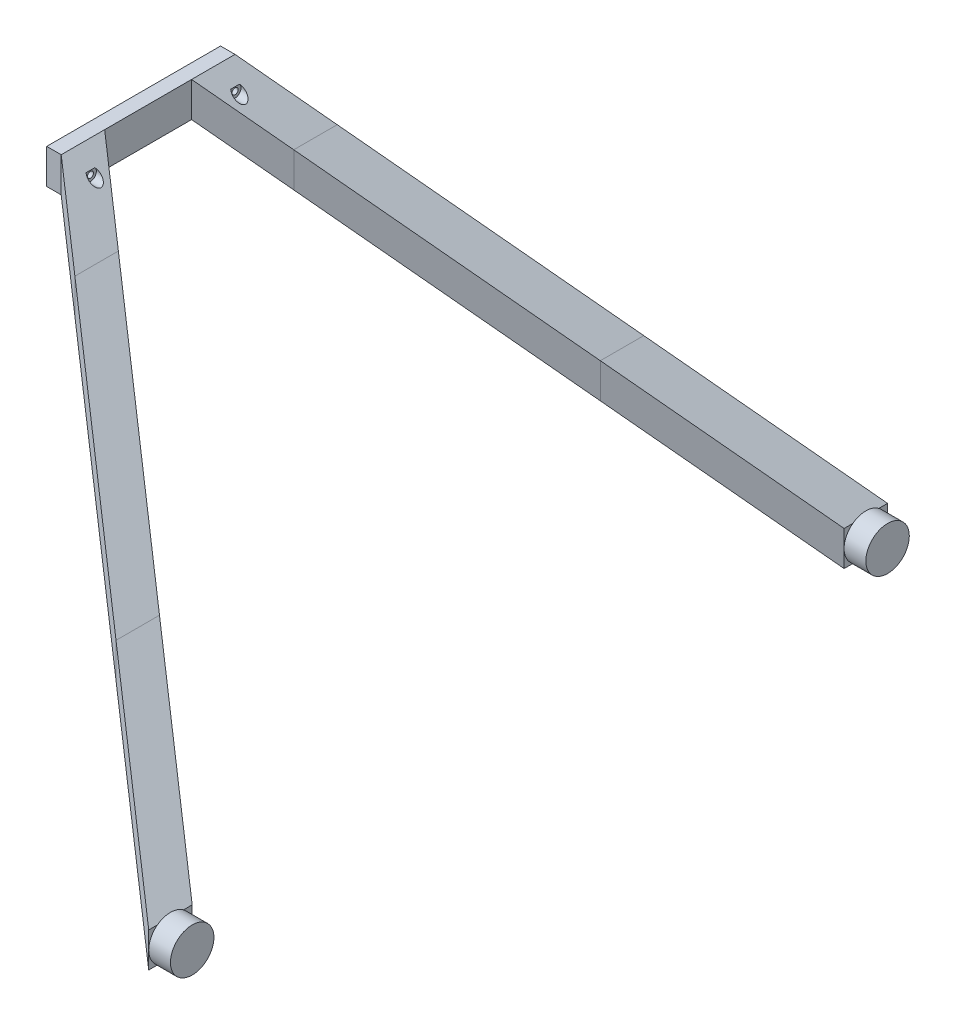
SolidWorks part; units mm, degrees
ref_plane "Front Plane" through (0, 0, 0) normal (1, 0, 0) x (0, 1, 0)
ref_plane "Top Plane" through (0, 0, 0) normal (0, 0, 1) x (0, 1, 0)
ref_plane "Right Plane" through (0, 0, 0) normal (0, 1, 0) x (-1, 0, 0)
sketch "Sketch2" plane through (0, 0, 0) normal (1, 0, 0) x (0, 1, 0)
  line L0 (-57.3564, 58.8048) -> (-57.3564, 65.8048) construction
  line L7 (2.4123, 2.5764) -> (-117.588, 2.5764) construction
  line L8 (-117.588, 122.576) -> (2.4123, 122.576) construction
  line L9 (-117.588, 122.576) -> (-117.588, 2.5764) construction
  line L10 (-93.588, 2.5764) -> (-117.588, 2.5764)
  line L11 (-117.588, 122.576) -> (-93.588, 122.576)
  line L12 (-117.588, 122.576) -> (-117.588, 2.5764)
  line L13 (-106.154, 114.414) -> (-105.708, 114.472) construction
  line L14 (-105.71, 14.6345) -> (-106.198, 14.5703) construction
  line L15 (-93.588, 122.576) -> (-93.588, 2.5764)
  circle A0 centre (-105.653, 112.38) radius 2.0816
  circle A2 centre (-105.655, 12.5418) radius 2.0822
  point P14 (-105.931, 114.443)
  point P19 (-105.954, 14.6024)
  dimension "D1" = 24
extrude "Boss-Extrude1" add sketch "Sketch2" along normal blind 10
sketch "Sketch5" plane through (0, 0, 2.5764) normal (0, 0, -1) x (1, 0, 0)
  line L0 (10, 117.588) -> (0, 108.2628)
  line L1 (0, -2.4123) -> (0, 117.588) construction
  line L2 (10, 117.588) -> (0, 117.588) construction
  dimension "D1" = 43
ref_plane "Plane2" through (-53.9996, -57.9074, 0) normal (-0.682, -0.7314, 0) x (-0.7314, 0.682, 0)
sketch "Sketch7" plane through (-53.9996, -57.9074, 0) normal (-0.682, -0.7314, 0) x (-0.7314, 0.682, 0)
  line L3 (-87.5084, -2.5764) -> (-436.7574, 192.4238)
  line L6 (-87.5084, -32.5764) -> (-436.7574, 162.4238)
  line L7 (-87.5084, -32.5764) -> (-87.5084, -2.5764)
  line L18 (-436.7574, 192.4238) -> (-436.7574, 162.4238)
  line L19 (-436.7574, -287.5762) -> (-436.7574, -317.5762)
  line L20 (-80.1948, -62.5762) -> (-87.5084, -62.5762) construction
  line L21 (-87.5084, -122.576) -> (-436.7574, -317.5762)
  line L22 (-87.5084, -92.576) -> (-87.5084, -122.576)
  line L23 (-87.5084, -92.576) -> (-436.7574, -287.5762)
  line L24 (-87.5084, -122.576) -> (-87.5084, -2.5764) construction
  line L25 (-87.5084, -2.5764) -> (-80.1948, -2.5764) construction
  line L26 (-87.5084, -122.576) -> (-80.1948, -122.576) construction
  line L27 (-80.1948, -122.576) -> (-80.1948, -2.5764) construction
  point P12 (-436.7574, 177.4238)
  point P15 (-436.7574, -302.5762)
  dimension "D2" = 400
  dimension "D3" = 480
  dimension "D1" = 30
extrude "Boss-Extrude2" add sketch "Sketch7" along direction (0, -1, 0) on the side against the normal up to vertex (17.5525 mm away) up to point (10, -93.588, 2.5764)
sketch "Sketch8" plane through (265.4246, 0, 0) normal (1, 0, 0) x (0, 1, 0)
  line L0 (-331.7753, 287.5762) -> (-331.7753, 317.5762) construction
  line L1 (-331.7753, 317.5762) -> (-355.7753, 317.5762) construction
  line L2 (-331.7753, -192.4238) -> (-331.7753, -162.4238) construction
  circle A0 centre (-343.7753, 302.5762) radius 15
  circle A1 centre (-343.7753, -177.4238) radius 15
  point P4 (-331.7753, 302.5762)
  point P7 (-343.7753, 317.5762)
  point P12 (-331.7753, -177.4238)
  dimension "D1" = 30
  dimension "D2" = 30
extrude "Boss-Extrude3" add sketch "Sketch8" along normal blind 15
sketch "Sketch9" plane through (10, 0, 0) normal (1, 0, 0) x (0, 1, 0)
  circle A0 centre (-105.655, 12.5418) radius 2.0822 construction
  circle A1 centre (-105.655, 12.5418) radius 2.0822
  circle A2 centre (-105.653, 112.38) radius 2.0816 construction
  circle A3 centre (-105.653, 112.38) radius 2.0816
extrude "Cut-Extrude1" cut sketch "Sketch9" along normal through all
sketch "Sketch10" plane through (10, 0, 0) normal (1, 0, 0) x (0, 1, 0)
  circle A2 centre (-105.655, 12.5418) radius 4.0822
  circle A3 centre (-105.655, 12.5418) radius 4.0822
  circle A6 centre (-105.653, 112.38) radius 4.0816
  circle A7 centre (-105.653, 112.38) radius 4.0816
  dimension "D1" = 2
  dimension "D2" = 2
extrude "Cut-Extrude2" cut sketch "Sketch10" along normal through all from offset 10
ref_plane "Plane3" through (50, 0, 0) normal (1, 0, 0) x (0, 0, -1)
split "Split1" trim tools "Plane3" bodies to split 116 resulting bodies 118 119 120
ref_plane "Plane4" through (170, 0, 0) normal (1, 0, 0) x (0, 0, -1)
split "Split2" trim tools "Plane4" bodies to split 119 118 resulting bodies 121 122 123 124
sketch "Sketch11" plane through (50, 0, 0) normal (1, 0, 0) x (0, 0, -1)
  line L8 (-150.1134, -151.8886) -> (-126.1134, -151.8886)
  line L9 (-150.1134, -133.8886) -> (-150.1134, -151.8886)
  line L10 (-126.1134, -133.8886) -> (-150.1134, -133.8886)
  line L11 (-126.1134, -151.8886) -> (-126.1134, -133.8886)
  line L12 (-150.1134, -151.8886) -> (-126.1134, -151.8886)
  line L13 (-150.1134, -133.8886) -> (-150.1134, -151.8886)
  line L14 (-126.1134, -133.8886) -> (-150.1134, -133.8886)
  line L15 (-126.1134, -151.8886) -> (-126.1134, -133.8886)
  dimension "D1" = 3
extrude "Cut-Extrude3" cut sketch "Sketch11" along direction (-0.6386, 0.5955, -0.4875) on the side of the normal blind 30
sketch "Sketch12" plane through (50, 0, 0) normal (1, 0, 0) x (0, 0, -1)
  line L8 (24.961, -151.8886) -> (24.961, -133.8886)
  line L9 (0.961, -151.8886) -> (24.961, -151.8886)
  line L10 (0.961, -133.8886) -> (0.961, -151.8886)
  line L11 (24.961, -133.8886) -> (0.961, -133.8886)
  line L12 (24.961, -151.8886) -> (24.961, -133.8886)
  line L13 (0.961, -151.8886) -> (24.961, -151.8886)
  line L14 (0.961, -133.8886) -> (0.961, -151.8886)
  line L15 (24.961, -133.8886) -> (0.961, -133.8886)
  dimension "D1" = 3
extrude "Cut-Extrude4" cut sketch "Sketch12" along direction (-0.6386, 0.5955, 0.4875) on the side of the normal blind 30
sketch "Sketch13" plane through (170, 0, 0) normal (1, 0, 0) x (0, 0, -1)
  line L8 (-241.7257, -263.7904) -> (-217.7257, -263.7904)
  line L9 (-241.7257, -245.7904) -> (-241.7257, -263.7904)
  line L10 (-217.7257, -263.7904) -> (-217.7257, -245.7904)
  line L11 (-217.7257, -245.7904) -> (-241.7257, -245.7904)
  line L12 (-241.7257, -263.7904) -> (-217.7257, -263.7904)
  line L13 (-241.7257, -245.7904) -> (-241.7257, -263.7904)
  line L14 (-217.7257, -263.7904) -> (-217.7257, -245.7904)
  line L15 (-217.7257, -245.7904) -> (-241.7257, -245.7904)
  dimension "D1" = 3
extrude "Cut-Extrude5" cut sketch "Sketch13" along direction (-0.6386, 0.5955, -0.4875) on the side of the normal blind 30
sketch "Sketch14" plane through (170, 0, 0) normal (1, 0, 0) x (0, 0, -1)
  line L8 (116.5733, -263.7904) -> (116.5733, -245.7904)
  line L9 (92.5733, -263.7904) -> (116.5733, -263.7904)
  line L10 (92.5733, -245.7904) -> (92.5733, -263.7904)
  line L11 (116.5733, -245.7904) -> (92.5733, -245.7904)
  line L12 (116.5733, -263.7904) -> (116.5733, -245.7904)
  line L13 (92.5733, -263.7904) -> (116.5733, -263.7904)
  line L14 (92.5733, -245.7904) -> (92.5733, -263.7904)
  line L15 (116.5733, -245.7904) -> (92.5733, -245.7904)
  dimension "D1" = 3
extrude "Cut-Extrude6" cut sketch "Sketch14" along direction (0.6386, -0.5955, -0.4875) on the side of the normal blind 30
sketch "Sketch15" plane through (50, 0, 0) normal (1, 0, 0) x (0, 0, -1)
  line L8 (-149.9134, -151.6886) -> (-126.3134, -151.6886)
  line L9 (-149.9134, -134.0886) -> (-149.9134, -151.6886)
  line L10 (-126.3134, -151.6886) -> (-126.3134, -134.0886)
  line L11 (-126.3134, -134.0886) -> (-149.9134, -134.0886)
  line L12 (-149.9134, -151.6886) -> (-126.3134, -151.6886)
  line L13 (-149.9134, -134.0886) -> (-149.9134, -151.6886)
  line L14 (-126.3134, -151.6886) -> (-126.3134, -134.0886)
  line L15 (-126.3134, -134.0886) -> (-149.9134, -134.0886)
  dimension "D1" = 3.2
extrude "Boss-Extrude4" add sketch "Sketch15" along direction (0.6386, -0.5955, 0.4875) on the side of the normal blind 30 separate body
sketch "Sketch16" plane through (50, 0, 0) normal (1, 0, 0) x (0, 0, -1)
  line L8 (24.761, -151.6886) -> (24.761, -134.0886)
  line L9 (1.161, -151.6886) -> (24.761, -151.6886)
  line L10 (24.761, -134.0886) -> (1.161, -134.0886)
  line L11 (1.161, -134.0886) -> (1.161, -151.6886)
  line L12 (24.761, -151.6886) -> (24.761, -134.0886)
  line L13 (1.161, -151.6886) -> (24.761, -151.6886)
  line L14 (24.761, -134.0886) -> (1.161, -134.0886)
  line L15 (1.161, -134.0886) -> (1.161, -151.6886)
  dimension "D1" = 3.2
extrude "Boss-Extrude5" add sketch "Sketch16" along direction (0.6386, -0.5955, -0.4875) on the side of the normal blind 30 separate body
combine bodies "Combine1" operation type add bodies to combine 120 130 129
sketch "Sketch17" plane through (170, 0, 0) normal (1, 0, 0) x (0, 0, -1)
  line L8 (-241.5257, -263.5904) -> (-217.9257, -263.5904)
  line L9 (-241.5257, -245.9904) -> (-241.5257, -263.5904)
  line L10 (-217.9257, -245.9904) -> (-241.5257, -245.9904)
  line L11 (-217.9257, -263.5904) -> (-217.9257, -245.9904)
  line L12 (-241.5257, -263.5904) -> (-217.9257, -263.5904)
  line L13 (-241.5257, -245.9904) -> (-241.5257, -263.5904)
  line L14 (-217.9257, -245.9904) -> (-241.5257, -245.9904)
  line L15 (-217.9257, -263.5904) -> (-217.9257, -245.9904)
  dimension "D1" = 3.2
extrude "Boss-Extrude6" add sketch "Sketch17" along direction (-0.6386, 0.5955, -0.4875) on the side of the normal blind 30 separate body
sketch "Sketch18" plane through (170, 0, 0) normal (1, 0, 0) x (0, 0, -1)
  line L8 (116.3733, -263.5904) -> (116.3733, -245.9904)
  line L9 (92.7733, -263.5904) -> (116.3733, -263.5904)
  line L10 (116.3733, -245.9904) -> (92.7733, -245.9904)
  line L11 (92.7733, -245.9904) -> (92.7733, -263.5904)
  line L12 (116.3733, -263.5904) -> (116.3733, -245.9904)
  line L13 (92.7733, -263.5904) -> (116.3733, -263.5904)
  line L14 (116.3733, -245.9904) -> (92.7733, -245.9904)
  line L15 (92.7733, -245.9904) -> (92.7733, -263.5904)
  dimension "D1" = 3.2
extrude "Boss-Extrude7" add sketch "Sketch18" along direction (0.6386, -0.5955, -0.4875) on the side of the normal blind 30 separate body
combine bodies "Combine2" operation type add bodies to combine 132 125
combine bodies "Combine3" operation type add bodies to combine 133 126
